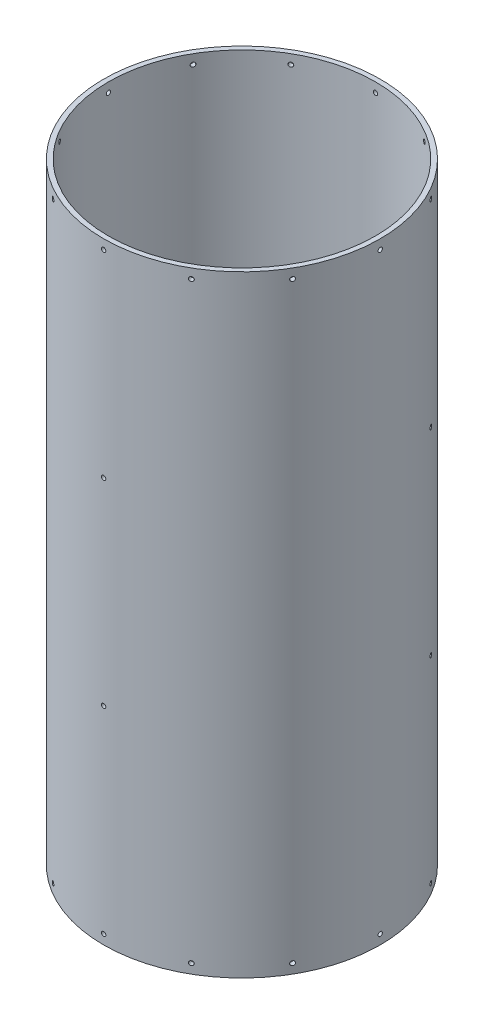
SolidWorks part; units mm, degrees
material "PVC Rigid"
ref_plane "Front Plane" through (0, 0, 0) normal (0, 0, 1) x (1, 0, 0)
ref_plane "Top Plane" through (0, 0, 0) normal (0, 1, 0) x (1, 0, 0)
ref_plane "Right Plane" through (0, 0, 0) normal (1, 0, 0) x (0, 0, -1)
sketch "Sketch1" plane through (0, 0, 0) normal (0, 1, 0) x (1, 0, 0)
  circle A0 centre (0, 0) radius 92.075
  circle A1 centre (0, 0) radius 88.9
  dimension "D1" = 184.15
  dimension "D2" = 177.8
extrude "Boss-Extrude1" add sketch "Sketch1" along normal mid plane 407.162
ref_plane "Plane1" through (0, 0, 92.075) normal (0, 0, 1) x (1, 0, 0)
sketch "Sketch3" plane through (0, 0, 92.075) normal (0, 0, 1) x (1, 0, 0)
  line L0 (0, -55) -> (0, 55) construction
  line L1 (-92.075, -203.581) -> (92.075, -203.581) construction
  circle A0 centre (0, -197.231) radius 1.4351
  dimension "D1" = 2.8702
  dimension "D2" = 6.35
extrude "Cut-Extrude1" cut sketch "Sketch3" against normal blind 19.304
pattern_circular "CirPattern1" count 12 over 360 about axis through (0, 203.581, 0) along (0, -1, 0) of "Cut-Extrude1" reverse direction yes
mirror "Mirror1" about plane through (0, 0, 0) normal (0, 1, 0) of "CirPattern1", "Cut-Extrude1"
sketch "Sketch4" plane through (0, 0, 92.075) normal (0, 0, 1) x (1, 0, 0)
  line L0 (0, -55) -> (0, 55) construction
  circle A0 centre (0, 65.7606) radius 1.4351
  circle A1 centre (0, -65.7606) radius 1.4351
  circle A2 centre (0, 197.231) radius 1.4351 construction
  circle A3 centre (0, -197.231) radius 1.4351 construction
  dimension "D1" = 131.4704
  dimension "D2" = 131.4704
  dimension "D3" = 2.8702
  dimension "D4" = 2.8702
extrude "Cut-Extrude2" cut sketch "Sketch4" against normal blind 43.18
pattern_circular "CirPattern2" count 3 over 360 about axis through (0, 203.581, 0) along (0, -1, 0) of "Cut-Extrude2" reverse direction yes
